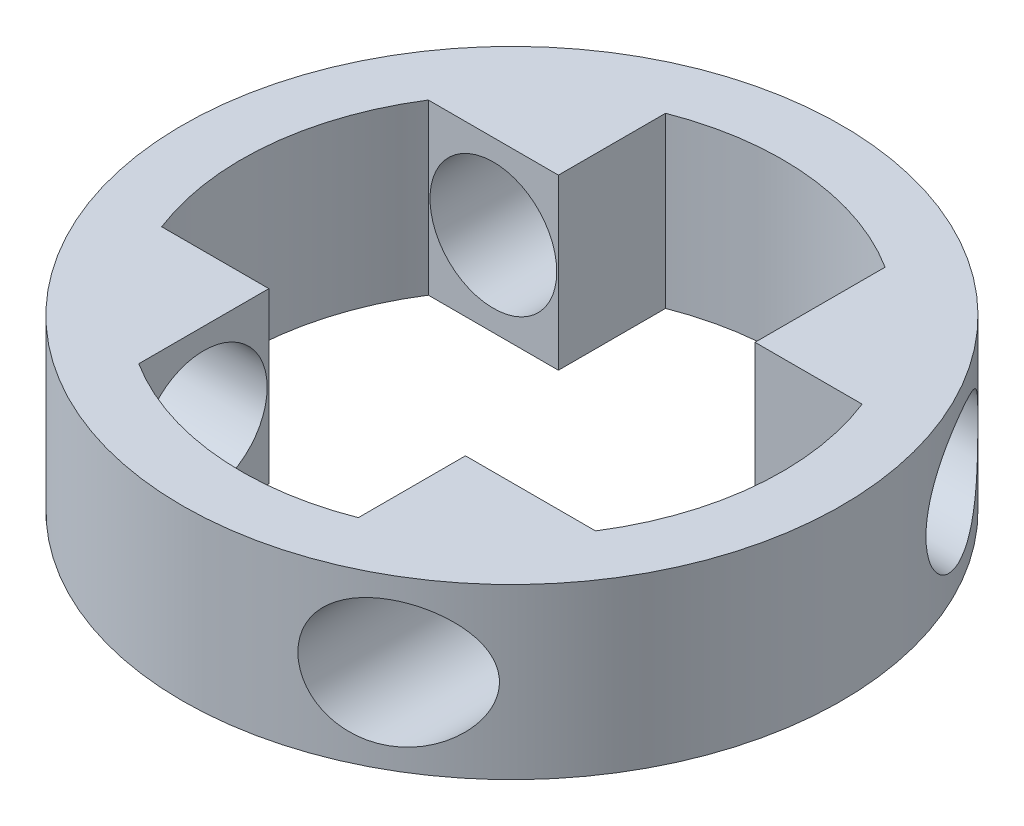
SolidWorks part; units mm, degrees
ref_plane "Front Plane" through (0, 0, 0) normal (0, 0, 1) x (1, 0, 0)
ref_plane "Top Plane" through (0, 0, 0) normal (0, 1, 0) x (1, 0, 0)
ref_plane "Right Plane" through (0, 0, 0) normal (1, 0, 0) x (0, 0, -1)
sketch "Sketch1" plane through (0, 0, 0) normal (0, 1, 0) x (1, 0, 0)
  circle A0 centre (0, 0) radius 49.53
  circle A1 centre (0, 0) radius 40.64
  dimension "D1" = 99.06
  dimension "D2" = 81.28
extrude "Boss-Extrude1" add sketch "Sketch1" along normal mid plane 25.4
sketch "Sketch2" plane through (0, 0, 0) normal (0, 1, 0) x (1, 0, 0)
  line L0 (32.5534, -32.5534) -> (-32.5534, -32.5534)
  line L1 (32.5534, -32.5534) -> (32.5534, 32.5534)
  line L2 (-32.5534, -32.5534) -> (-32.5534, 32.5534)
  line L3 (32.5534, 32.5534) -> (-32.5534, 32.5534)
  line L5 (-14.7734, 21.7584) -> (-50.3334, 21.7584)
  line L6 (-14.7734, 21.7584) -> (-14.7734, 43.3484)
  line L7 (-14.7734, 43.3484) -> (-50.3334, 43.3484)
  line L8 (-50.3334, 21.7584) -> (-50.3334, 43.3484)
  line L9 (-14.7734, 21.7584) -> (-50.3334, 43.3484) construction
  line L10 (-14.7734, 43.3484) -> (-50.3334, 21.7584) construction
  line L11 (-21.7584, -50.3334) -> (-43.3484, -50.3334)
  line L12 (-21.7584, -50.3334) -> (-21.7584, -14.7734)
  line L13 (-21.7584, -14.7734) -> (-43.3484, -14.7734)
  line L14 (-43.3484, -50.3334) -> (-43.3484, -14.7734)
  line L15 (-21.7584, -50.3334) -> (-43.3484, -14.7734) construction
  line L16 (-21.7584, -14.7734) -> (-43.3484, -50.3334) construction
  line L17 (21.7584, 14.7734) -> (43.3484, 14.7734)
  line L18 (21.7584, 14.7734) -> (21.7584, 50.3334)
  line L19 (21.7584, 50.3334) -> (43.3484, 50.3334)
  line L20 (43.3484, 14.7734) -> (43.3484, 50.3334)
  line L21 (21.7584, 14.7734) -> (43.3484, 50.3334) construction
  line L22 (21.7584, 50.3334) -> (43.3484, 14.7734) construction
  line L23 (14.7734, -21.7584) -> (50.3334, -21.7584)
  line L24 (14.7734, -21.7584) -> (14.7734, -43.3484)
  line L25 (14.7734, -43.3484) -> (50.3334, -43.3484)
  line L26 (50.3334, -21.7584) -> (50.3334, -43.3484)
  line L27 (14.7734, -21.7584) -> (50.3334, -43.3484) construction
  line L28 (14.7734, -43.3484) -> (50.3334, -21.7584) construction
  circle A0 centre (0, 0) radius 43.18 construction
  circle A1 centre (0, 0) radius 48.895
  circle A2 centre (0, 0) radius 46.0375 construction
  dimension "D1" = 5.715
  dimension "D2" = 2.8575
  dimension "D3" = 97.79
  dimension "D4" = 65.1069
  dimension "D5" = 21.59
  dimension "D6" = 35.56
  dimension "D7" = 35.56
  dimension "D8" = 21.59
  dimension "D9" = 35.56
  dimension "D10" = 21.59
  dimension "D11" = 21.59
  dimension "D12" = 35.56
extrude "Boss-Extrude2" add sketch "Sketch2" along normal mid plane 25.4 contours L7 A1 L8 L5 L2 L3 L6 | L5 L6 L3 L2 | L18 L17 L1 L3 | L20 A1 L19 L18 L3 L1 L17 | L25 A1 L26 L23 L1 L0 L24 | L23 L24 L0 L1 | L14 A1 L11 L12 L0 L2 L13 | L12 L13 L2 L0 region at (27.7052, 0, 33.5215) region at (23.6634, 0, 27.1559) region at (-33.5215, 0, 27.7052) region at (-27.1559, 0, 23.6634) region at (27.1559, 0, -23.6634) region at (33.5215, 0, -27.7052) region at (-27.7052, 0, -33.5215) region at (-23.6634, 0, -27.1559)
sketch "Sketch3" plane through (-21.7584, 0, 0) normal (1, 0, 0) x (0, 0, -1)
  line L0 (-24.549, 12.7) -> (-24.549, -12.7) construction
  line L1 (-34.3246, -12.7) -> (-14.7734, -12.7) construction
  line L2 (-34.3246, -12.7) -> (-34.3246, 12.7) construction
  line L3 (-34.3246, 12.7) -> (-14.7734, 12.7) construction
  line L4 (-14.7734, -12.7) -> (-14.7734, 12.7) construction
  line L5 (-34.3246, 0) -> (-14.7734, 0) construction
  circle A0 centre (-24.549, 0) radius 9.525
  dimension "D1" = 19.05
extrude "Cut-Extrude1" cut sketch "Sketch3" against normal through all
pattern_circular "CirPattern1" count 4 over 360 about axis through (0, 12.7, 0) along (0, 1, 0) of "Cut-Extrude1"
